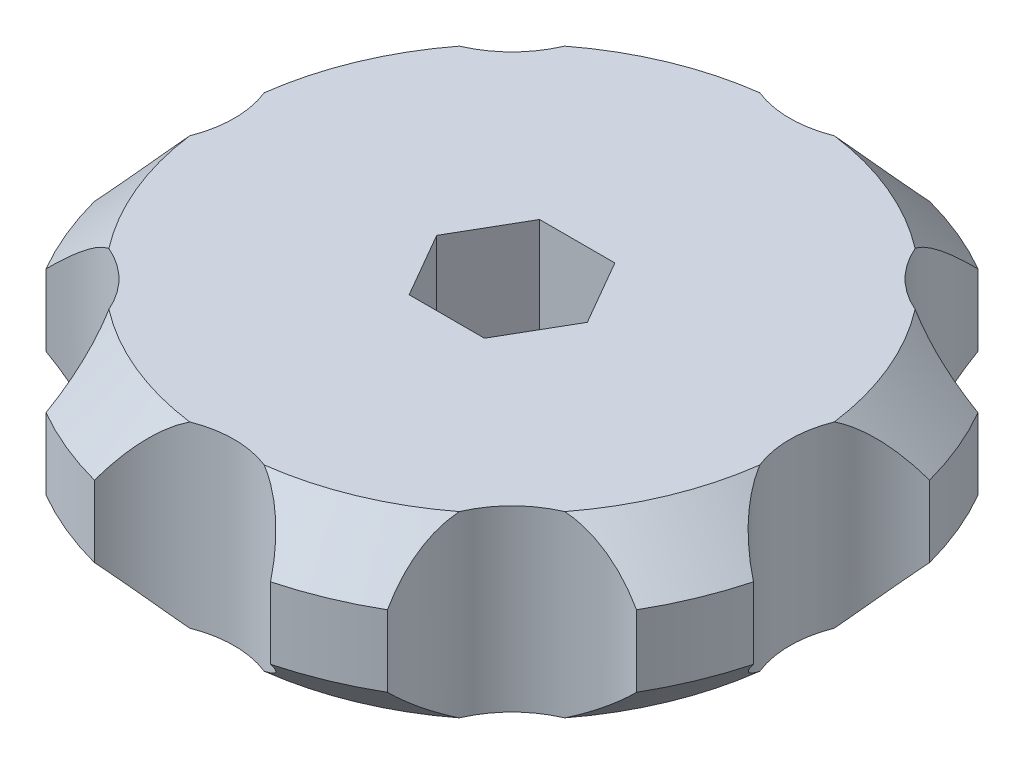
SolidWorks part; units mm, degrees
ref_plane "Front Plane" through (0, 0, 0) normal (0, 0, 1) x (1, 0, 0)
ref_plane "Top Plane" through (0, 0, 0) normal (0, 1, 0) x (1, 0, 0)
ref_plane "Right Plane" through (0, 0, 0) normal (1, 0, 0) x (0, 0, -1)
sketch "Sketch1" plane through (0, 0, 0) normal (0, 1, 0) x (1, 0, 0)
  line L0 (0, -21.2055) -> (21.2055, -21.2055) construction
  line L1 (0, -21.2055) -> (14.9946, -14.9946) construction
  line L2 (14.9946, -14.9946) -> (21.2055, 0) construction
  line L3 (21.2055, 0) -> (14.9946, 14.9946) construction
  line L4 (14.9946, 14.9946) -> (0, 21.2055) construction
  line L5 (0, 21.2055) -> (-14.9946, 14.9946) construction
  line L6 (-14.9946, 14.9946) -> (-21.2055, 0) construction
  line L7 (-21.2055, 0) -> (-14.9946, -14.9946) construction
  line L8 (-14.9946, -14.9946) -> (0, -21.2055) construction
  line L9 (21.2055, -21.2055) -> (21.2055, 0) construction
  arc A1 (4.9292, -18.444) -> (-4.9292, -18.444) centre (0, -21.2055) ccw
  arc A2 (-9.5565, -16.5274) -> (-16.5274, -9.5565) centre (-14.9946, -14.9946) ccw
  arc A3 (-18.444, -4.9292) -> (-18.444, 4.9292) centre (-21.2055, 0) ccw
  arc A4 (-16.5274, 9.5565) -> (-9.5565, 16.5274) centre (-14.9946, 14.9946) ccw
  arc A5 (-4.9292, 18.444) -> (4.9292, 18.444) centre (0, 21.2055) ccw
  arc A6 (9.5565, 16.5274) -> (16.5274, 9.5565) centre (14.9946, 14.9946) ccw
  arc A7 (-9.5565, -16.5274) -> (-4.9292, -18.444) centre (0, 0) ccw
  arc A8 (-16.5274, -9.5565) -> (-18.444, -4.9292) centre (0, 0) cw
  arc A9 (-18.444, 4.9292) -> (-16.5274, 9.5565) centre (0, 0) cw
  arc A10 (-9.5565, 16.5274) -> (-4.9292, 18.444) centre (0, 0) cw
  arc A11 (4.9292, 18.444) -> (9.5565, 16.5274) centre (0, 0) cw
  arc A13 (18.444, 4.9292) -> (18.444, -4.9292) centre (21.2055, 0) ccw
  arc A14 (16.5274, -9.5565) -> (9.5565, -16.5274) centre (14.9946, -14.9946) ccw
  arc A15 (4.9292, -18.444) -> (9.5565, -16.5274) centre (0, 0) ccw
  arc A16 (16.5274, -9.5565) -> (18.444, -4.9292) centre (0, 0) ccw
  arc A17 (18.444, 4.9292) -> (16.5274, 9.5565) centre (0, 0) ccw
  circle A18 centre (0, 0) radius 19.5913 construction
  point P23 (0, 0)
  point P27 (-4.9292, -18.444)
  point P29 (-4.9292, -18.444)
  point P31 (-7.3059, -17.6381)
  point P33 (-7.4973, -18.1)
  point P37 (-9.5565, -16.5274)
  dimension "D1" = 16.23
  dimension "D2" = 0.5
  dimension "D3" = 5.65
  dimension "D4" = 8
extrude "Boss-Extrude1" add sketch "Sketch1" along normal blind 10
chamfer "Chamfer1" distance 3 angle 45 16 edges at (-7.3059, 0, -17.6381) (7.3059, 0, -17.6381) (17.6381, 0, -7.3059) (17.6381, 0, 7.3059) (7.3059, 0, 17.6381) (-7.3059, 0, 17.6381) (-17.6381, 0, 7.3059) (-17.6381, 0, -7.3059) (-17.6381, 10, -7.3059) (-7.3059, 10, -17.6381) (7.3059, 10, -17.6381) (17.6381, 10, -7.3059) (17.6381, 10, 7.3059) (7.3059, 10, 17.6381) (-7.3059, 10, 17.6381) (-17.6381, 10, 7.3059)
sketch "Sketch2" plane through (0, 10, 0) normal (0, 1, 0) x (1, 0, 0)
  line L1 (-2.1073, -3.65) -> (2.1073, -3.65)
  line L2 (2.1073, -3.65) -> (4.2147, 0)
  line L3 (4.2147, 0) -> (2.1073, 3.65)
  line L4 (2.1073, 3.65) -> (-2.1073, 3.65)
  line L5 (-2.1073, 3.65) -> (-4.2147, 0)
  line L6 (-4.2147, 0) -> (-2.1073, -3.65)
  circle A0 centre (0, 0) radius 3.65 construction
  dimension "D1" = 7.3
extrude "Cut-Extrude1" cut sketch "Sketch2" against normal through all
